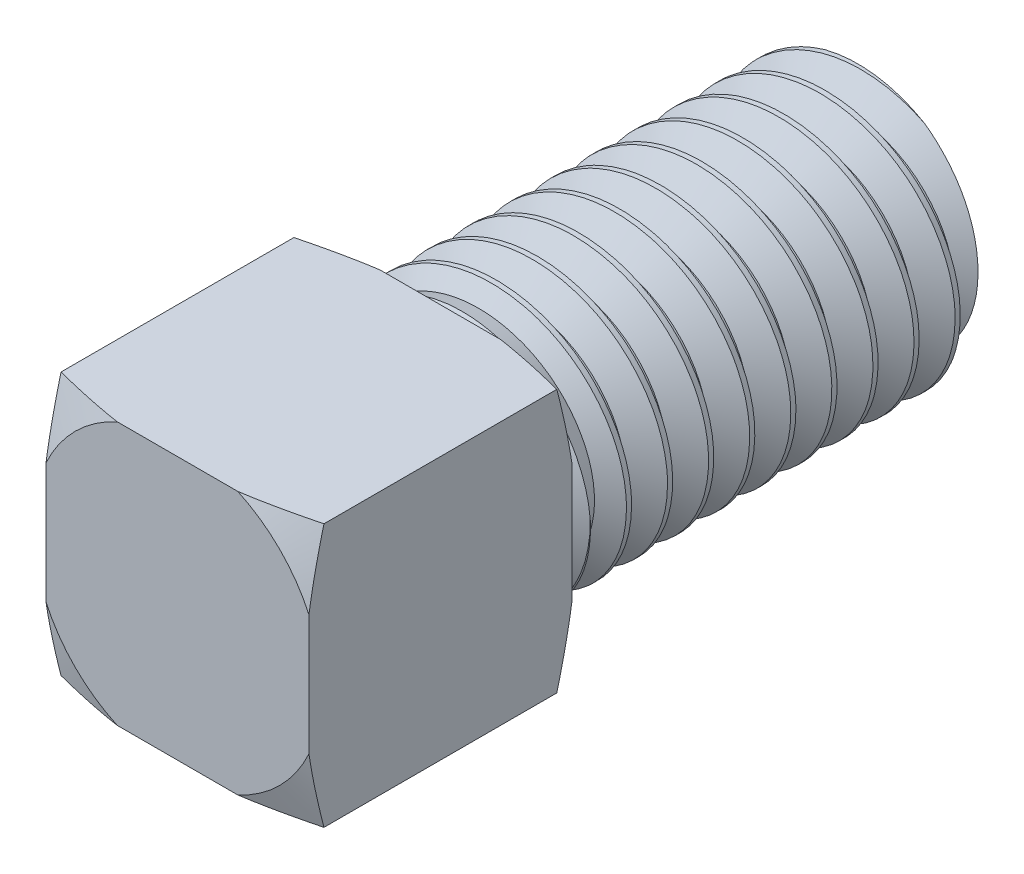
SolidWorks part; units mm, degrees
note: The reader was unsure of these and kept them because the rebuilt part matched: shared geometry of "Sketch25<2>".
ref_plane "Front" through (0, 0, 0) normal (0, 0, 1) x (1, 0, 0)
ref_plane "Top" through (0, 0, 0) normal (0, 1, 0) x (1, 0, 0)
ref_plane "Right" through (0, 0, 0) normal (1, 0, 0) x (0, 0, -1)
sketch "Sketch22" plane through (0, 0, 0) normal (1, 0, 0) x (0, 0, -1)
  line L0 (-12.5, 0) -> (-12.5, 3.2)
  line L1 (-12.5, 3.2) -> (-11.9398, 4)
  line L2 (-11.9398, 4) -> (9, 4)
  line L3 (9, 4) -> (10.25, 2.75)
  line L5 (12.5, 0) -> (-12.5, 0)
  line L6 (13, 0) -> (10.25, 0) construction
  line L7 (10.25, 0) -> (10.25, 2.75) construction
  line L9 (-11.9398, -4) -> (9, -4) construction
  line L10 (10.25, 2.75) -> (12.5, 2.75)
  line L11 (12.5, 2.75) -> (12.5, 0)
  line L12 (12.5, 2.75) -> (12.5, -2.75) construction
  dimension "Screw Dia" = 8
  dimension "D3" = 35
  dimension "D6" = 45
  dimension "D7" = 6.4
  dimension "A" = 5.5
  dimension "B" = 2.25
  dimension "Length" = 25
revolve "Revolve1" add sketch "Sketch22" angle 360 about L6
ref_plane "Plane2" through (0, 0, -10.25) normal (0, 0, 1) x (1, 0, 0)
sketch "Sketch27" plane through (0, 0, -10.25) normal (0, 0, 1) x (1, 0, 0)
  circle A0 centre (0, 0) radius 4
curve "Helix/Spiral1" pitch 1.25 height 26.25 turns 21
sketch "Sketch6" plane through (0, 0, 0) normal (1, 0, 0) x (0, 0, -1)
  line L0 (10.4844, 3.5941) -> (11.1094, 3.5941) construction
  line L3 (-11.9398, 4) -> (9, 4) construction
  line L4 (10.875, 3.1881) -> (10.7187, 3.1881)
  line L5 (10.7187, 3.1881) -> (10.25, 4)
  line L6 (10.875, 3.1881) -> (11.3437, 4)
  line L7 (11.3437, 4) -> (10.25, 4)
  dimension "D2" = 0.1562
  dimension "D3" = 60
  dimension "D1" = 0.625
sweep "Cut-Sweep1" cut profiles "Sketch6" path "Helix/Spiral1"
sketch "Sketch23" plane through (0, 0, 12.5) normal (0, 0, 1) x (1, 0, 0)
  line L0 (-4, 4) -> (-4, -4)
  line L1 (-4, -4) -> (4, -4)
  line L2 (4, -4) -> (4, 4)
  line L3 (4, 4) -> (-4, 4)
  line L4 (-4, -4) -> (4, 4) construction
  dimension "Head Width" = 8
extrude "Extrude1" add sketch "Sketch23" along normal blind 8
sketch "Sketch25" plane through (0, 0, 20.5) normal (0, 0, 1) x (1, 0, 0)
  circle A0 centre (0, 0) radius 4.4
  dimension "D1" = 8.8
extrude "Cut-Extrude1" cut sketch "Sketch25" against normal through all draft 70 flip side to cut
extrude "Cut-Extrude2" cut sketch "Sketch25<2>" along normal through all draft 70 from vertex at -8 flip side to cut starting at point (-4, -4, 12.5)
sketch "Sketch25<2>" plane through (0, 0, 20.5) normal (0, 0, 1) x (1, 0, 0) same geometry as "Sketch25"
sketch "Sketch28" plane through (0, 0, 12.5) normal (0, 0, -1) x (-1, 0, 0)
  line L1 (0, 4) -> (0, 3.7333) construction
  line L2 (0, 3.7333) -> (0, 3.4667) construction
  line L3 (0, 3.4667) -> (0, 3.2) construction
  circle A0 centre (0, 0) radius 3.7333
extrude "Boss-Extrude1" add sketch "Sketch28" along normal up to body draft 15 separate body
sketch "Sketch29" plane through (0, 0, 0) normal (1, 0, 0) x (0, 0, -1)
  line L0 (-20.5, -1.833) -> (-20.5, 1.833) construction
  line L2 (-11.9398, -4) -> (9, -4) construction
  point P0 (-20.5, 4)
  point P1 (-12.5, 4)
  point P2 (10.25, 2.75)
  point P3 (12.5, 2.75)
  point P4 (12.5, -2.75)
  point P5 (12.5, -4)
  point P6 (5.25, -4)
  point P7 (12.5, 4)
  dimension "D1" = 3.75
sketch "Sketch30" plane through (0, 0, -12.5) normal (0, 0, -1) x (-1, 0, 0)
  line L1 (-6.4207, 5.6648) -> (6.4207, 5.6648)
  line L2 (-6.4207, 5.6648) -> (-6.4207, -5.6648)
  line L3 (-6.4207, -5.6648) -> (6.4207, -5.6648)
  line L4 (6.4207, 5.6648) -> (6.4207, -5.6648)
  line L5 (-6.4207, 5.6648) -> (6.4207, -5.6648) construction
  line L6 (-6.4207, -5.6648) -> (6.4207, 5.6648) construction
  point P0 (0, 0)
extrude "Cut-Extrude3" cut sketch "Sketch30" against normal blind 12.3
equation "\"D7@Sketch22\"=\"Screw Dia@Sketch22\"*.8"
equation "\"D1@Sketch25\" = \"Screw Dia@Sketch22\" * 1.1"
equation "\"D3@Helix/Spiral1\" = \"Length@Sketch22\" + \"D4@Helix/Spiral1\""
equation "\"D2@Sketch6\" = \"D4@Helix/Spiral1\" * .125"
equation "\"D1@Sketch6\" = \"D4@Helix/Spiral1\" * .5"
equation "\"D1@Sketch29\" = \"D4@Helix/Spiral1\" * 3"
